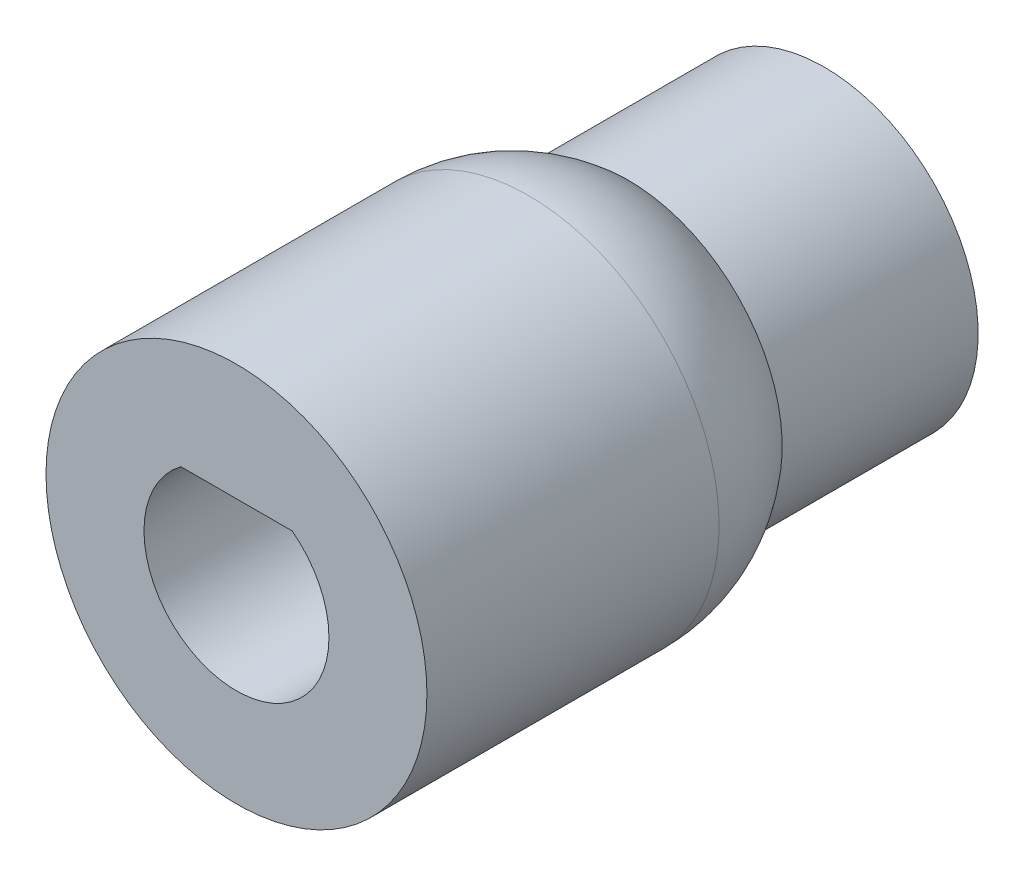
SolidWorks part; units mm, degrees
ref_plane "Front" through (0, 0, 0) normal (0, 0, 1) x (1, 0, 0)
ref_plane "Top" through (0, 0, 0) normal (0, 1, 0) x (1, 0, 0)
ref_plane "Right" through (0, 0, 0) normal (1, 0, 0) x (0, 0, -1)
sketch "Sketch1" plane through (0, 0, 0) normal (0, 0, 1) x (1, 0, 0)
  line L0 (-1.8034, 2.3939) -> (1.8034, 2.3939)
  circle A0 centre (0, 0) radius 2.9972
  circle A1 centre (0, 0) radius 6.1722
  dimension "D1" = 5.9944
  dimension "D3" = 3.6068
  dimension "D2" = 3.175
extrude "Boss-Extrude1" add sketch "Sketch1" along normal blind 12.7 contours L0 A0 | A1 A0 region at (0, 2.6375, 0) region at (-5.9976, 0, 0)
sketch "Sketch2" plane through (0, 0, 0) normal (0, 0, -1) x (-1, 0, 0)
  circle A0 centre (0, 0) radius 1.985
  circle A1 centre (0, 0) radius 4.985
  dimension "D1" = 3.97
  dimension "D2" = 3
extrude "Boss-Extrude2" add sketch "Sketch2" along normal blind 6.35
fillet "Fillet1" radius 5 1 edges at (6.1722, 0, 0)
